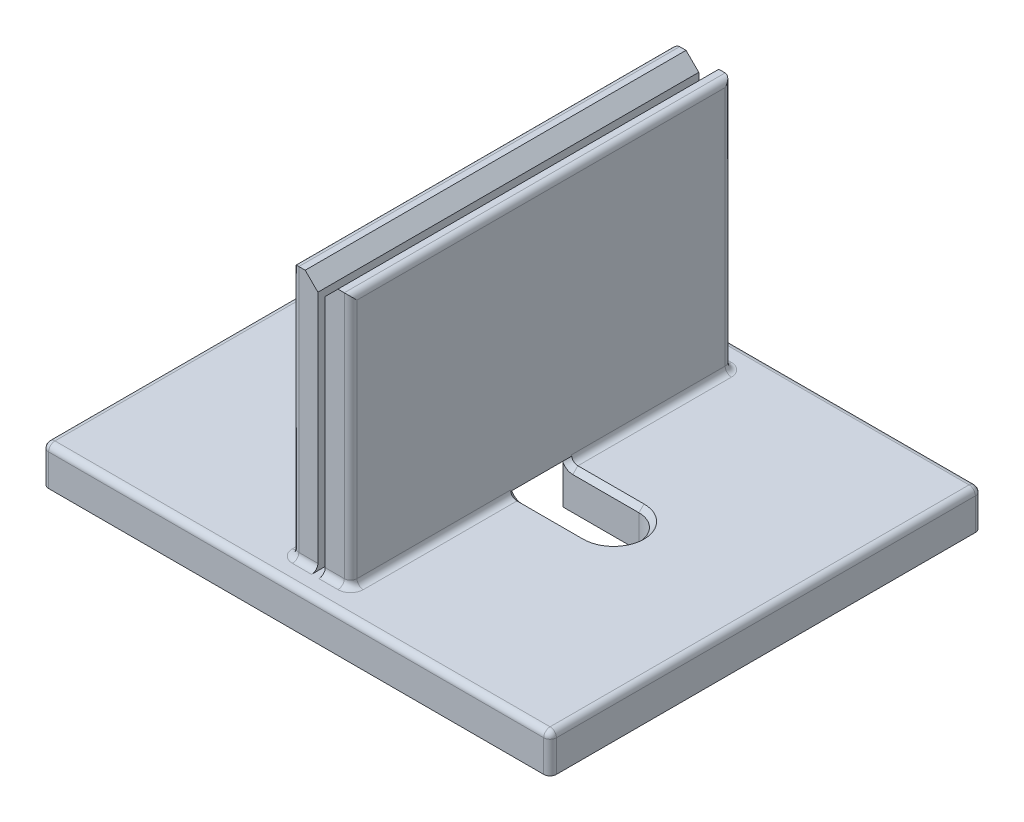
SolidWorks part; units mm, degrees
ref_plane "Спереди" through (0, 0, 0) normal (0, 0, 1) x (1, 0, 0)
ref_plane "Сверху" through (0, 0, 0) normal (0, 1, 0) x (1, 0, 0)
ref_plane "Справа" through (0, 0, 0) normal (1, 0, 0) x (0, 0, -1)
other "Configuration Table"
sketch "Эскиз1" plane through (0, 0, 0) normal (0, 1, 0) x (1, 0, 0)
  line L1 (-100, 85) -> (100, 85)
  line L2 (-100, 85) -> (-100, -85)
  line L3 (-100, -85) -> (100, -85)
  line L4 (100, 85) -> (100, -85)
  line L5 (-100, 85) -> (100, -85) construction
  line L6 (-100, -85) -> (100, 85) construction
  point P0 (0, 0)
  dimension "D1" = 170
  dimension "D2" = 200
extrude "Бобышка-Вытянуть1" add sketch "Эскиз1" along normal blind 15
sketch "Эскиз2" plane through (0, 15, 0) normal (0, 1, 0) x (1, 0, 0)
  line L0 (0, 50) -> (0, -50) construction
  line L1 (10, 50) -> (10, -50)
  line L2 (-10, 50) -> (-10, -50)
  line L3 (40, 0) -> (-40, 0) construction
  line L4 (40, -10) -> (-40, -10)
  line L5 (40, 10) -> (-40, 10)
  arc A0 (10, 50) -> (-10, 50) centre (0, 50) ccw
  arc A1 (-10, -50) -> (10, -50) centre (0, -50) ccw
  arc A2 (40, -10) -> (40, 10) centre (40, 0) ccw
  arc A3 (-40, 10) -> (-40, -10) centre (-40, 0) ccw
  point P2 (0, 0)
  point P10 (0, 0)
  dimension "D2" = 10
  dimension "D3" = 10
  dimension "D1" = 100
  dimension "D4" = 80
extrude "Вырез-Вытянуть1" cut sketch "Эскиз2" against normal through all both and the other way through all contours L1 A0 L2 L5 | L2 A1 L1 L4 | L5 A3 L4 L2 | L1 L5 L2 L4 | L4 A2 L5 L1 region at (0, 15, -33.979) region at (28.9928, 15, 0) region at (0, 15, 0) region at (0, 15, 33.979) region at (-28.9928, 15, 0)
sketch "Эскиз3" plane through (0, 0, 0) normal (0, 0, 1) x (1, 0, 0)
  line L0 (0, 0) -> (0, 78.9364) construction
  line L1 (-100, 15) -> (100, 15) construction
  line L2 (-1.45, 15) -> (-11.45, 15)
  line L3 (-1.45, 15) -> (-1.45, 115)
  line L4 (-1.45, 115) -> (-11.45, 115)
  line L5 (-11.45, 15) -> (-11.45, 115)
  dimension "D1" = 10
  dimension "D2" = 2.9
  dimension "D3" = 100
extrude "Бобышка-Вытянуть2" add sketch "Эскиз3" along normal mid plane 150
chamfer "Фаска1" distance 5 angle 45 1 edges at (-1.45, 115, 0)
mirror "Зеркальное отражение1" about plane through (0, 0, 0) normal (1, 0, 0) of "Фаска1", "Бобышка-Вытянуть2"
fillet "Скругление1" radius 2.5 22 edges at (11.45, 115, 0) (-11.45, 115, 0) (-11.45, 65, -75) (-11.45, 65, 75) (11.45, 65, 75) (11.45, 65, -75) (-100, 7.5, -85) (0, 15, -85) (100, 7.5, -85) (100, 15, 0) (100, 7.5, 85) (-100, 7.5, 85) (0, 15, 85) (-100, 15, 0) (-6.45, 15, -75) (6.45, 15, -75) (11.45, 15, -42.5) (11.45, 15, 42.5) (6.45, 15, 75) (-6.45, 15, 75) (-11.45, 15, -42.5) (-11.45, 15, 42.5)
chamfer "Фаска2" distance 2 angle 45 10 edges at (-12.1822, 15.7322, -10) (-26.975, 15, -10) (-12.1822, 15.7322, 10) (-50, 15, 0) (-26.975, 15, 10) (12.1822, 15.7322, -10) (26.975, 15, -10) (50, 15, 0) (12.1822, 15.7322, 10) (26.975, 15, 10)
chamfer "Фаска3" distance 2 angle 45 2 edges at (-11.45, 15, 0) (11.45, 15, 0)
